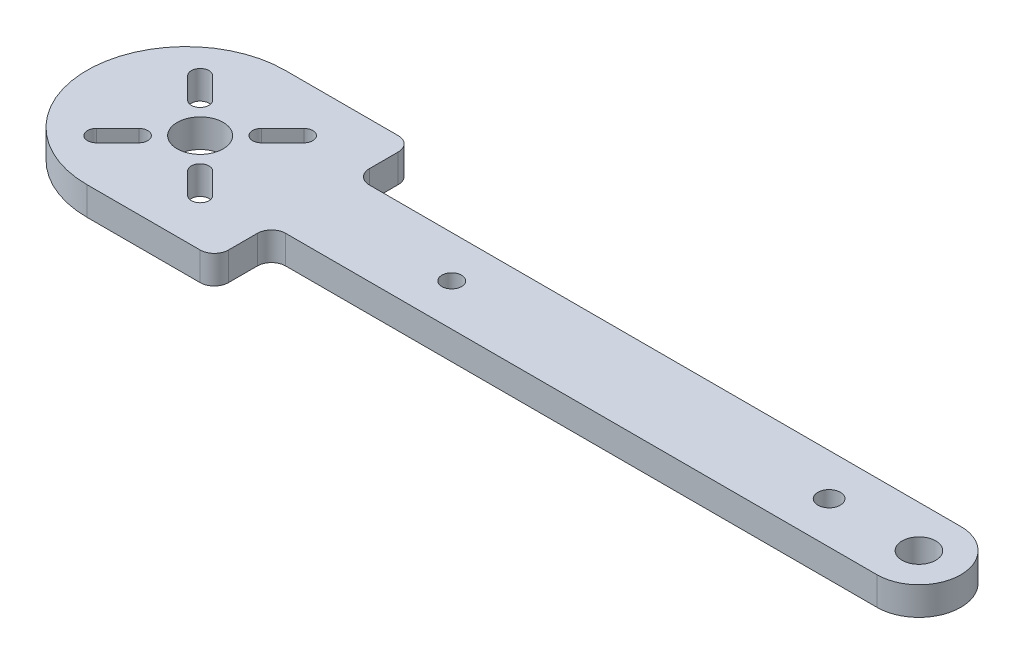
SolidWorks part; units mm, degrees
material "Thornel VCB-20 Carbon Cloth"
ref_plane "Front Plane" through (0, 0, 0) normal (0, 0, 1) x (1, 0, 0)
ref_plane "Top Plane" through (0, 0, 0) normal (0, 1, 0) x (1, 0, 0)
ref_plane "Right Plane" through (0, 0, 0) normal (1, 0, 0) x (0, 0, -1)
sketch "Sketch1" plane through (0, 0, 0) normal (0, 1, 0) x (1, 0, 0)
  line L0 (-58.0134, 7.2134) -> (-43.5866, -7.2134) construction
  line L1 (-50.8, 14) -> (-36.8, 14)
  line L2 (-50.8, 14) -> (-50.8, -14) construction
  line L3 (-50.8, -14) -> (-36.8, -14)
  line L7 (-58.4887, -7.6887) -> (-43.1113, 7.6887) construction
  line L8 (-58.1362, 7.3362) -> (-55.131, 4.331) construction
  line L9 (-57.2523, 8.2201) -> (-54.2471, 5.2149)
  line L10 (-59.0201, 6.4523) -> (-56.0149, 3.4471)
  line L11 (-43.4638, 7.3362) -> (-46.469, 4.331) construction
  line L12 (-42.5799, 6.4523) -> (-45.5851, 3.4471)
  line L13 (-44.3477, 8.2201) -> (-47.3529, 5.2149)
  line L14 (-43.4638, -7.3362) -> (-46.469, -4.331) construction
  line L15 (-44.3477, -8.2201) -> (-47.3529, -5.2149)
  line L16 (-42.5799, -6.4523) -> (-45.5851, -3.4471)
  line L17 (-58.1362, -7.3362) -> (-55.131, -4.331) construction
  line L18 (-59.0201, -6.4523) -> (-56.0149, -3.4471)
  line L19 (-57.2523, -8.2201) -> (-54.2471, -5.2149)
  line L21 (-34.8, 7.9146) -> (-34.8, 12)
  line L24 (-34.8, -12) -> (-34.8, -7.9146)
  line L32 (-32.8, 5.9146) -> (50.8, 5.9146)
  line L33 (-32.8, -5.9146) -> (50.8, -5.9146)
  line L34 (-50.8, 0) -> (50.8, 0) construction
  line L35 (-50.8, 14) -> (-52.8, 14)
  line L36 (-50.8, -14) -> (-52.8, -14)
  circle A2 centre (-50.8, 0) radius 3.25
  arc A3 (-57.2523, 8.2201) -> (-59.0201, 6.4523) centre (-58.1362, 7.3362) ccw
  arc A4 (-56.0149, 3.4471) -> (-54.2471, 5.2149) centre (-55.131, 4.331) ccw
  arc A5 (-42.5799, 6.4523) -> (-44.3477, 8.2201) centre (-43.4638, 7.3362) ccw
  arc A6 (-47.3529, 5.2149) -> (-45.5851, 3.4471) centre (-46.469, 4.331) ccw
  arc A7 (-44.3477, -8.2201) -> (-42.5799, -6.4523) centre (-43.4638, -7.3362) ccw
  arc A8 (-45.5851, -3.4471) -> (-47.3529, -5.2149) centre (-46.469, -4.331) ccw
  arc A9 (-59.0201, -6.4523) -> (-57.2523, -8.2201) centre (-58.1362, -7.3362) ccw
  arc A10 (-54.2471, -5.2149) -> (-56.0149, -3.4471) centre (-55.131, -4.331) ccw
  circle A11 centre (50.8, 0) radius 2.3813
  arc A12 (-34.8, -7.9146) -> (-32.8, -5.9146) centre (-32.8, -7.9146) cw
  arc A13 (-32.8, 5.9146) -> (-34.8, 7.9146) centre (-32.8, 7.9146) cw
  arc A14 (-36.8, -14) -> (-34.8, -12) centre (-36.8, -12) ccw
  arc A15 (-34.8, 12) -> (-36.8, 14) centre (-36.8, 12) ccw
  arc A16 (50.8, 5.9146) -> (50.8, -5.9146) centre (50.8, 0) cw
  arc A17 (-52.8, -14) -> (-52.8, 14) centre (-52.8, 0) cw
  circle A18 centre (-15.24, 0) radius 1.397
  point P0 (0, 0)
  point P12 (-50.8, 0)
  point P14 (-50.8, 0)
  point P17 (-56.6336, 5.8336)
  point P27 (-44.9664, 5.8336)
  point P34 (-44.9664, -5.8336)
  point P41 (-56.6336, -5.8336)
  point P46 (-50.8, 0)
  point P53 (-34.8, -7)
  point P56 (-34.8, 7)
  point P59 (-34.8, -14)
  point P62 (-34.8, 14)
  dimension "D3" = 6.5
  dimension "D6" = 8.25
  dimension "D10" = 4.7625
  dimension "D17" = 2
  dimension "D18" = 2
  dimension "D16" = 5.9146
  dimension "D2" = 14
  dimension "D21" = 2.794
  dimension "D22" = 66.04
  dimension "D4" = 45
  dimension "D5" = 45
  dimension "D7" = 4.25
  dimension "D8" = 2.5
  dimension "D11" = 16
  dimension "D12" = 16
  dimension "D13" = 7
  dimension "D14" = 7
  dimension "D15" = 101.6
  dimension "D19" = 50.8
  dimension "D20" = 2
  dimension "D9" = 4
extrude "Boss-Extrude1" add sketch "Sketch1" along normal blind 4
sketch "Sketch2" plane through (0, 0, 0) normal (0, -1, 0) x (1, 0, 0)
  circle A0 centre (38.1, 0) radius 1.5875
  circle A1 centre (50.8, 0) radius 2.3813 construction
  dimension "D1" = 3.175
  dimension "D2" = 12.7
extrude "Cut-Extrude1" cut sketch "Sketch2" against normal blind 10
